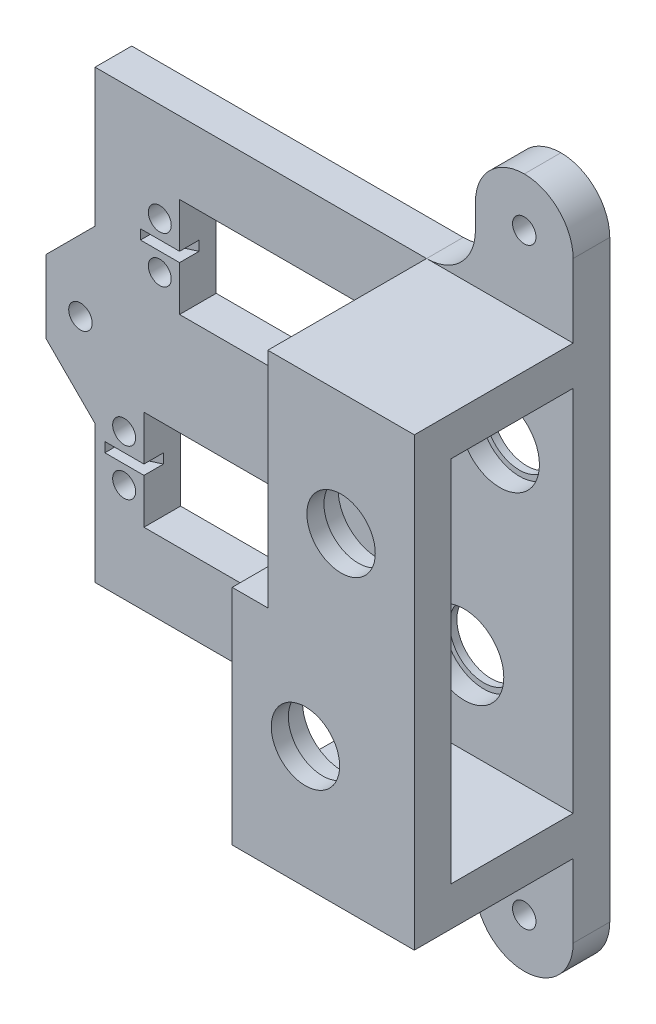
SolidWorks part; units mm, degrees
ref_plane "Front Plane" through (0, 0, 0) normal (0, 0, 1) x (1, 0, 0)
ref_plane "Top Plane" through (0, 0, 0) normal (0, 1, 0) x (1, 0, 0)
ref_plane "Right Plane" through (0, 0, 0) normal (1, 0, 0) x (0, 0, -1)
sketch "Sketch1" plane through (0, 0, 0) normal (0, 0, 1) x (1, 0, 0)
  line L0 (-15, 0) -> (22.2932, 0)
  line L5 (-15, 91.3619) -> (22.2932, 91.3619)
  line L6 (-15, 0) -> (-15, 91.3619)
  line L7 (22.2932, 0) -> (22.2932, 91.3619)
  line L8 (0, 25) -> (7.2932, 66.3619) construction
  line L9 (0, 25) -> (0, 79.2) construction
  circle A1 centre (0, 25) radius 8.1
  circle A2 centre (7.2932, 66.3619) radius 8.1
  point P4 (0, 0)
  dimension "D2" = 16.2
  dimension "D5" = 25
  dimension "D4" = 15
  dimension "D6" = 25
  dimension "D8" = 42
  dimension "D9" = 10
  dimension "D10" = 15
extrude "Boss-Extrude1" add sketch "Sketch1" along normal blind 40
ref_plane "INNER WALL" through (0, 0, 39) normal (0, 0, 1) x (1, 0, 0)
ref_plane "OUTER WALL" through (0, 0, 32.65) normal (0, 0, 1) x (1, 0, 0)
sketch "Sketch2" plane through (0, 0, 0) normal (0, 1, 0) x (1, 0, 0)
  line L1 (-15, -7.5) -> (22.2932, -7.5)
  line L2 (-15, -7.5) -> (-15, -32.5)
  line L3 (-15, -32.5) -> (22.2932, -32.5)
  line L4 (22.2932, -7.5) -> (22.2932, -32.5)
  line L6 (-15, -40) -> (-15, 0) construction
  line L7 (22.2932, -40) -> (22.2932, 0) construction
  point P9 (22.2932, -20)
  point P10 (22.2932, -20)
  dimension "D1" = 25
extrude "Cut-Extrude1" cut sketch "Sketch2" along normal through all from offset 8
sketch "Sketch10" plane through (0, 0, 40) normal (0, 0, 1) x (1, 0, 0)
  circle A0 centre (7.2932, 66.3619) radius 8.1
  circle A1 centre (0, 25) radius 10.837
  circle A2 centre (7.2932, 66.3619) radius 7
  circle A3 centre (0, 25) radius 7
  circle A4 centre (7.2932, 66.3619) radius 8.1 construction
  circle A5 centre (0, 25) radius 8.1 construction
  dimension "D2" = 14
  dimension "D4" = 14
extrude "Boss-Extrude2" add sketch "Sketch10" against normal offset from surface (3.5 mm away) 4 up to face at (-8.1, 25, 32.5)
sketch "Sketch11" plane through (0, 0, 0) normal (0, 0, -1) x (-1, 0, 0)
  circle A0 centre (-7.2932, 66.3619) radius 8.1
  circle A1 centre (-7.2932, 66.3619) radius 7
  circle A2 centre (0, 25) radius 8.1
  circle A3 centre (0, 25) radius 7
  circle A4 centre (0, 25) radius 8.1 construction
  circle A5 centre (-7.2932, 66.3619) radius 8.1 construction
  dimension "D1" = 14
  dimension "D2" = 14
extrude "Boss-Extrude3" add sketch "Sketch11" against normal offset from surface (3.5 mm away) 4 up to face at (8.1, 25, 7.5)
ref_axis "Axis1" through (0, 25, 3.5) along (0, 0, -1)
ref_plane "Plane1" through (0, 25, 0) normal (0, -1, 0) x (-1, 0, 0)
ref_axis "Axis2" through (7.2932, 66.3619, 3.5) along (0, 0, -1)
ref_plane "Plane2" through (0, 66.3619, 0) normal (0, -1, 0) x (-1, 0, 0)
sketch "Sketch12" plane through (0, 0, 0) normal (0, 0, -1) x (-1, 0, 0)
  line L0 (-20.5113, 25) -> (20.5113, 25) construction
  line L1 (15, 0) -> (75.56, 0)
  line L2 (15, 0) -> (15, 91.3619)
  line L3 (15, 91.3619) -> (75.56, 91.3619)
  line L5 (-20.5113, 66.3619) -> (20.5113, 66.3619) construction
  line L6 (24.66, 35.2) -> (65.56, 35.2)
  line L7 (24.66, 35.2) -> (24.66, 14.8)
  line L8 (24.66, 14.8) -> (65.56, 14.8)
  line L9 (65.56, 35.2) -> (65.56, 14.8)
  line L10 (-22.2932, 91.3619) -> (15, 91.3619) construction
  line L11 (17.3668, 76.5619) -> (58.2668, 76.5619)
  line L12 (17.3668, 76.5619) -> (17.3668, 56.1619)
  line L13 (17.3668, 56.1619) -> (58.2668, 56.1619)
  line L14 (58.2668, 76.5619) -> (58.2668, 56.1619)
  line L16 (15, 0) -> (-22.2932, 0) construction
  line L17 (15, 91.3619) -> (15, 0) construction
  line L20 (75.56, 91.3619) -> (75.56, 0)
  line L21 (58.2668, 56.1619) -> (58.2668, 35.2) construction
  line L22 (45.11, 35.2) -> (45.11, 14.8) construction
  line L32 (37.8168, 76.5619) -> (37.8168, 56.1619) construction
  circle A0 centre (35, 25) radius 6.6 construction
  circle A1 centre (0, 25) radius 7 construction
  circle A2 centre (27.7068, 66.3619) radius 6.6 construction
  circle A3 centre (-7.2932, 66.3619) radius 7 construction
  point P4 (75.56, 91.3619)
  point P15 (45.11, 14.8)
  point P16 (74.8844, 91.3619)
  point P27 (17.3668, 66.3619)
  point P34 (37.8168, 56.1619)
  point P53 (45.11, 25)
  dimension "D7" = 13.2
  dimension "D11" = 13.2
  dimension "D2" = 20.4
  dimension "D3" = 40.9
  dimension "D4" = 10.11
  dimension "D9" = 10.11
  dimension "D5" = 35
  dimension "D6" = 10
extrude "Boss-Extrude4" add sketch "Sketch12" against normal up to surface (7.5 mm away) up to face at (8.1, 25, 7.5)
sketch "Sketch13" plane through (0, 0, 0) normal (0, 0, -1) x (-1, 0, 0)
  line L0 (24.66, 35.2) -> (24.66, 14.8) construction
  line L1 (-20.5113, 25) -> (20.5113, 25) construction
  line L2 (65.56, 14.8) -> (65.56, 35.2) construction
  line L3 (17.3668, 76.5619) -> (17.3668, 56.1619) construction
  line L5 (-20.5113, 66.3619) -> (20.5113, 66.3619) construction
  line L6 (58.2668, 56.1619) -> (58.2668, 76.5619) construction
  circle A0 centre (20.61, 29.75) radius 2.3495
  circle A1 centre (20.61, 20.25) radius 2.3495
  circle A2 centre (69.61, 29.75) radius 2.3495
  circle A3 centre (69.61, 20.25) radius 2.3495
  circle A4 centre (13.3168, 71.1119) radius 2.3495
  circle A5 centre (13.3168, 61.6119) radius 2.3495
  circle A6 centre (62.3168, 71.1119) radius 2.3495
  circle A7 centre (62.3168, 61.6119) radius 2.3495
  dimension "D1" = 4.699
  dimension "D2" = 4.05
  dimension "D3" = 9.5
  dimension "D4" = 4.75
  dimension "D5" = 4.05
  dimension "D7" = 9.5
  dimension "D8" = 4.05
  dimension "D9" = 4.75
  dimension "D10" = 4.05
extrude "Cut-Extrude2" cut sketch "Sketch13" against normal up to next
sketch "Sketch22" plane through (0, 0, 7.5) normal (0, 0, 1) x (1, 0, 0)
  line L0 (-58.2668, 56.1619) -> (-58.2668, 76.5619) construction
  line L1 (-58.2668, 65.3619) -> (-66.2668, 65.3619)
  line L2 (-58.2668, 65.3619) -> (-58.2668, 67.3619)
  line L3 (-58.2668, 67.3619) -> (-66.2668, 67.3619)
  line L4 (-66.2668, 65.3619) -> (-66.2668, 67.3619)
  line L5 (-17.3668, 76.5619) -> (-17.3668, 56.1619) construction
  line L6 (-17.3668, 65.3619) -> (-9.3668, 65.3619)
  line L7 (-17.3668, 65.3619) -> (-17.3668, 67.3619)
  line L8 (-17.3668, 67.3619) -> (-9.3668, 67.3619)
  line L9 (-9.3668, 65.3619) -> (-9.3668, 67.3619)
  line L10 (-24.66, 35.2) -> (-24.66, 14.8) construction
  line L11 (-24.66, 24) -> (-16.66, 24)
  line L12 (-24.66, 24) -> (-24.66, 26)
  line L13 (-24.66, 26) -> (-16.66, 26)
  line L14 (-16.66, 24) -> (-16.66, 26)
  line L15 (-65.56, 14.8) -> (-65.56, 35.2) construction
  line L16 (-65.56, 24) -> (-73.56, 24)
  line L17 (-65.56, 24) -> (-65.56, 26)
  line L18 (-65.56, 26) -> (-73.56, 26)
  line L19 (-73.56, 24) -> (-73.56, 26)
  point P24 (-58.2668, 66.3619)
  point P25 (-66.2668, 66.3619)
  point P26 (-73.56, 25)
  point P27 (-65.56, 25)
  dimension "D1" = 2
  dimension "D2" = 8
extrude "Cut-Extrude6" cut sketch "Sketch22" against normal blind 2
sketch "Sketch14" plane through (0, 0, 7.5) normal (0, 0, 1) x (1, 0, 0)
  line L0 (22.2932, 0) -> (22.2932, 91.3619) construction
  line L1 (22.2932, 91.3619) -> (-15, 91.3619)
  line L2 (22.2932, 91.3619) -> (22.2932, 83.3619)
  line L3 (22.2932, 83.3619) -> (-15, 83.3619)
  line L4 (-15, 91.3619) -> (-15, 83.3619)
  line L5 (22.2932, 91.3619) -> (-15, 91.3619) construction
  line L6 (-15, 91.3619) -> (-15, 0) construction
  dimension "D1" = 8
extrude "Boss-Extrude5" add sketch "Sketch14" along normal up to surface (25 mm away) up to face at (-8.1, 25, 32.5)
sketch "Sketch18" plane through (0, 0, 40) normal (0, 0, 1) x (1, 0, 0)
  line L0 (7.2932, 66.3619) -> (7.2932, 25) construction
  line L1 (-15, 91.3619) -> (-7.7068, 91.3619)
  line L2 (-15, 91.3619) -> (-15, 45.681)
  line L3 (-15, 45.681) -> (-7.7068, 45.681)
  line L4 (-7.7068, 91.3619) -> (-7.7068, 45.681)
  line L5 (0, 25) -> (7.2932, 25) construction
  circle A0 centre (7.2932, 66.3619) radius 8.1 construction
  point P13 (7.2932, 45.681)
  dimension "D1" = 15
extrude "Cut-Extrude4" cut sketch "Sketch18" against normal up to surface (32.5 mm away) up to face at (-45.11, 25, 7.5)
sketch "Sketch15" plane through (0, 0, 0) normal (0, 0, -1) x (-1, 0, 0)
  circle A0 centre (0, 25) radius 11
  circle A1 centre (-7.2932, 66.3619) radius 11
  dimension "D1" = 22
extrude "Cut-Extrude3" cut sketch "Sketch15" against normal blind 2
chamfer "Chamfer2" distance 2 angle 65 4 edges at (-65.56, 25, 5.5) (-58.2668, 66.3619, 5.5) (-17.3668, 66.3619, 5.5) (-24.66, 25, 5.5) first distance on face at (-65.56, 25, 5.125) first distance on face at (-58.2668, 66.3619, 5.125) first distance on face at (-17.3668, 66.3619, 5.125) first distance on face at (-24.66, 25, 5.125)
sketch "Sketch23" plane through (0, 0, 7.5) normal (0, 0, 1) x (1, 0, 0)
  line L0 (-15, 0) -> (22.2932, 0) construction
  line L1 (2.2932, 0) -> (22.2932, 0)
  line L2 (2.2932, 0) -> (2.2932, -25)
  line L3 (2.2932, -25) -> (22.2932, -25)
  line L4 (22.2932, 0) -> (22.2932, -25)
  line L5 (22.2932, 0) -> (22.2932, 91.3619) construction
  line L6 (22.2932, 91.3619) -> (2.2932, 91.3619)
  line L7 (22.2932, 91.3619) -> (22.2932, 116.3619)
  line L8 (22.2932, 116.3619) -> (2.2932, 116.3619)
  line L9 (2.2932, 91.3619) -> (2.2932, 116.3619)
  line L10 (-75.56, 0) -> (-75.56, 91.3619) construction
  line L11 (-75.56, 38.181) -> (-85.56, 38.181)
  line L12 (-75.56, 38.181) -> (-75.56, 53.181)
  line L13 (-75.56, 53.181) -> (-85.56, 53.181)
  line L14 (-85.56, 38.181) -> (-85.56, 53.181)
  point P19 (-75.56, 45.681)
  point P20 (-85.56, 45.681)
  dimension "D1" = 20
  dimension "D2" = 25
  dimension "D3" = 15
  dimension "D4" = 10
extrude "Boss-Extrude6" add sketch "Sketch23" against normal up to surface (7.5 mm away) up to face at (-11, 25, 0)
fillet "Fillet1" radius 10 6 edges at (2.2932, 116.3619, 3.75) (22.2932, 116.3619, 3.75) (22.2932, -25, 3.75) (2.2932, -25, 3.75) (2.2932, 0, 3.75) (2.2932, 91.3619, 3.75)
chamfer "Chamfer3" distance 10 angle 45 2 edges at (-75.56, 38.181, 3.75) (-75.56, 53.181, 3.75)
sketch "Sketch24" plane through (0, 0, 7.5) normal (0, 0, 1) x (1, 0, 0)
  line L0 (-85.56, 53.181) -> (-85.56, 38.181) construction
  point P0 (12.2932, 106.3619)
  point P3 (12.2932, -15)
  point P6 (-78.56, 45.681)
  point P11 (0, 0)
  dimension "D1" = 7
hole_wizard "M4 Clearance Hole1" positions "Sketch24" profile "Sketch25" hole size "M4" standard "ANSI Metric" end condition through all
sketch "Sketch25" plane through (12.2932, 106.3619, 7.5) normal (1, 0, 0) x (0, -1, 0)
  line L0 (0, 0) -> (0, 7.5)
  line L1 (0, 7.5) -> (2.4, 7.5)
  line L2 (2.4, 7.5) -> (2.4, 0)
  line L5 (2.4, 0) -> (0, 0)
  line L11 (0, -6.35) -> (0, 107.95) construction
  dimension "Thru Hole Dia." = 4.8
  dimension "Thru Hole Depth" = 7.5
equation "\"D4@Sketch13\"=\"D3@Sketch13\"/2"
equation "\"D5@Sketch12\"=\"D1@Sketch12\""
equation "\"D8@Sketch13\"=\"D2@Sketch13\""
equation "\"D9@Sketch13\"=\"D7@Sketch13\"/2"
equation "\"D10@Sketch13\"=\"D5@Sketch13\""
